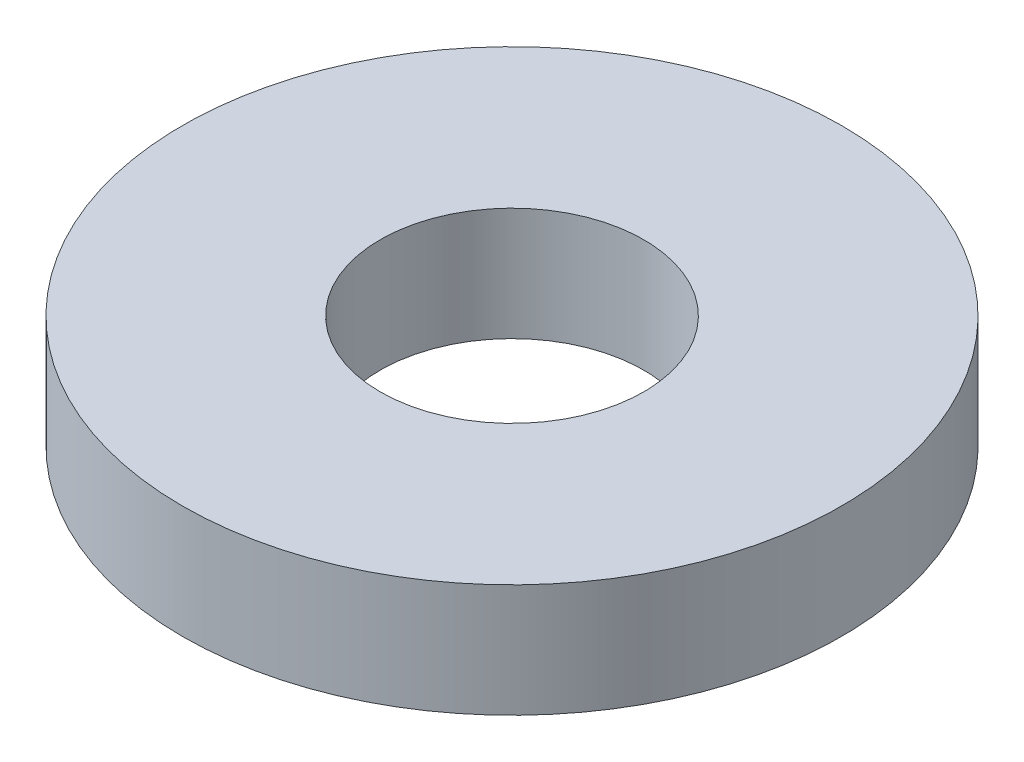
SolidWorks part; units mm, degrees
ref_plane "Front Plane" through (0, 0, 0) normal (0, 0, 1) x (1, 0, 0)
ref_plane "Top Plane" through (0, 0, 0) normal (0, 1, 0) x (1, 0, 0)
ref_plane "Right Plane" through (0, 0, 0) normal (1, 0, 0) x (0, 0, -1)
sketch "Sketch1" plane through (0, 0, 0) normal (0, 1, 0) x (1, 0, 0)
  circle A0 centre (0, 0) radius 87.5
  dimension "FLANGE_OD" = 175
extrude "Boss-Extrude1" add sketch "Sketch1" along normal blind 30
sketch "Sketch2" plane through (0, 0, 0) normal (0, 1, 0) x (1, 0, 0)
  circle A0 centre (0, 0) radius 35
  dimension "BORE_D" = 70
extrude "Cut-Extrude1" cut sketch "Sketch2" along normal through all
sketch "Sketch3" plane through (0, 30, 0) normal (0, 1, 0) x (1, 0, 0)
  circle A0 centre (0, 0) radius 24.0886 construction
  circle A1 centre (-24.0886, 0) radius 7.4133
  dimension "BOLT_D" = 14.8267
  dimension "BOLT_PCD" = 48.1771
extrude "Cut-Extrude2" cut sketch "Sketch3" against normal blind 25.683 rebuild error yes
pattern_circular "CirPattern1" count 4 over 360 rebuild error yes
